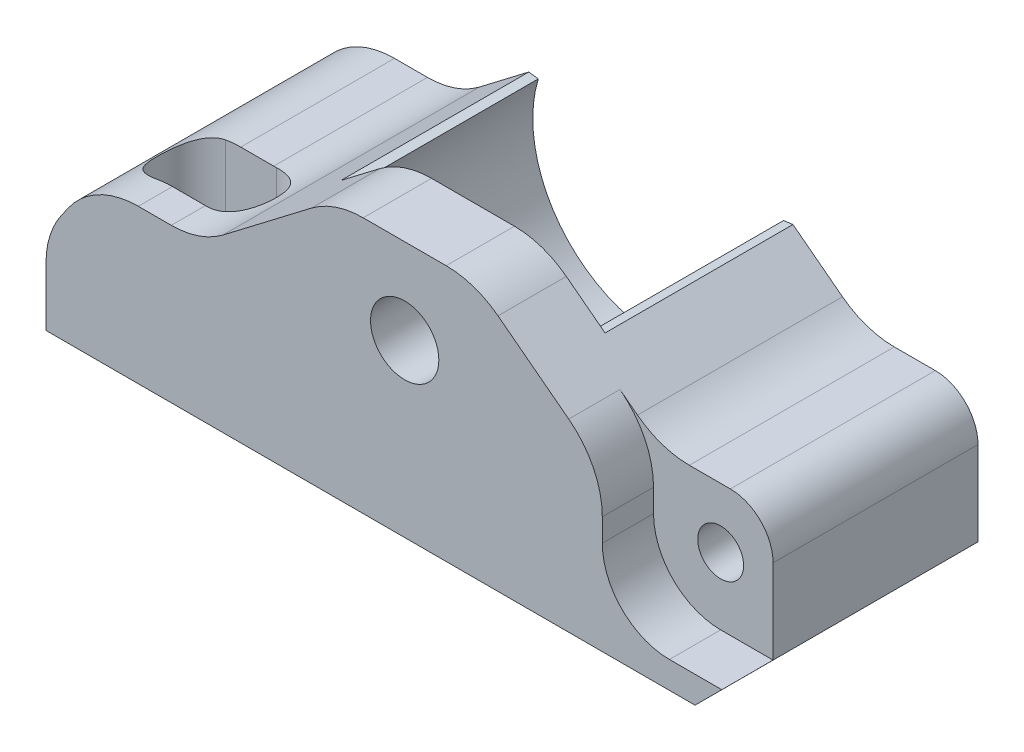
SolidWorks part; units mm, degrees
material "ABS generico"
ref_plane "Piano frontale" through (0, 0, 0) normal (0, 0, 1) x (1, 0, 0)
ref_plane "Piano superiore" through (0, 0, 0) normal (0, 1, 0) x (1, 0, 0)
ref_plane "Piano destro" through (0, 0, 0) normal (1, 0, 0) x (0, 0, -1)
sketch "Schizzo2" plane through (0, 0, 0) normal (0, 0, 1) x (1, 0, 0)
  line L0 (-40, 0) -> (-2, 0)
  line L1 (-40, 0) -> (-40, 9)
  line L2 (-19, 0) -> (-19, 25.5566) construction
  line L3 (-40, 9) -> (-30.9754, 9)
  line L4 (-30.9754, 9) -> (-23.1199, 15)
  line L5 (-23.1199, 15) -> (-14.8801, 15)
  line L6 (-7.0246, 9) -> (-14.8801, 15)
  line L7 (-0.4334, 9) -> (-7.0246, 9)
  line L8 (-0.4334, 1.5666) -> (-2, 0)
  line L11 (-0.4334, 9) -> (-0.4334, 1.5666)
  circle A0 centre (-19, 10) radius 2
  circle A1 centre (-3.5, 5.5) radius 1.3432
  point P0 (-40, 0)
  point P1 (2, 0)
  point P10 (-19, 15)
  dimension "D3" = 4
  dimension "D4" = 15
  dimension "D1" = 42
  dimension "D2" = 9
  dimension "D5" = 10
  dimension "D6" = 15.5
  dimension "D7" = 5.5
  dimension "D9" = 4
extrude "Estrusione-Estrusione1" add sketch "Schizzo2" against normal blind 15
sketch "Schizzo3" plane through (0, 0, -15) normal (0, 0, -1) x (-1, 0, 0)
  circle A0 centre (19, 10) radius 7.5
  circle A1 centre (19, 10) radius 2 construction
  dimension "D1" = 15
extrude "Taglio-Estrusione1" cut sketch "Schizzo3" against normal blind 11
sketch "Schizzo4" plane through (0, 0, 0) normal (0, 0, 1) x (1, 0, 0)
  line L2 (-7.4302, 9.334) -> (-0.4334, 9.334)
  line L3 (-0.4334, 9.334) -> (-0.4334, 1.5698)
  line L6 (-7.4302, 5.5) -> (-7.4302, 9.334)
  line L7 (-3.5, 1.5698) -> (-0.4334, 1.5698)
  arc A1 (-7.4302, 5.5) -> (-3.5, 1.5698) centre (-3.5, 5.5) ccw
extrude "Taglio-Estrusione2" cut sketch "Schizzo4" against normal blind 3
chamfer "Smusso3" distance 1 angle 45 2 edges at (-12.0614, 12.8471, -9.5) (-25.9386, 12.8471, -9.5) first distance on face at (-10.3491, 11.5392, -5.5) first distance on face at (-26.678, 12.2824, -6.3333)
fillet "Raccordo1" radius 2.5 1 edges at (-0.4334, 9, -9)
chamfer "Smusso4" distance 4 angle 35 1 edges at (-40, 9, -7.5) first distance on face at (-40, 4.5, -7.5)
sketch "Schizzo5" plane through (0, 0, 0) normal (0, -1, 0) x (1, 0, 0)
  line L0 (0, -4) -> (39.5666, -4) construction
  line L2 (-35.5, -4) -> (-32.5, -4) construction
  line L3 (-40, 0) -> (-2, 0) construction
  line L4 (-35.5, -2) -> (-32.5, -2)
  line L5 (-35.5, -6) -> (-32.5, -6)
  arc A1 (-35.5, -2) -> (-35.5, -6) centre (-35.5, -4) ccw
  arc A2 (-32.5, -6) -> (-32.5, -2) centre (-32.5, -4) ccw
  point P10 (-34, -4)
  dimension "D2" = 4
  dimension "D4" = 4
  dimension "D5" = 3
extrude "Taglio-Estrusione3" cut sketch "Schizzo5" against normal through all
fillet "Fillet1" radius 5 1 edges at (-7.0246, 9, -9)
fillet "Fillet2" radius 5 1 edges at (-7.4302, 9.4608, -1.5)
fillet "Fillet3" radius 5 2 edges at (-40, 5, -7.5) (-37.1992, 9, -1.4725)
fillet "Fillet4" radius 5 2 edges at (-23.1199, 15, -2) (-14.8801, 15, -2)
fillet "Fillet5" radius 5 1 edges at (-30.9754, 9, -1.3528)
